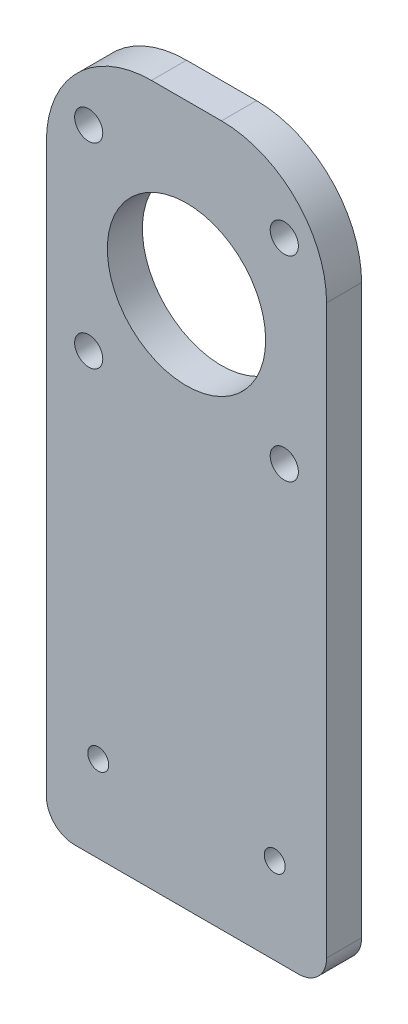
SolidWorks part; units mm, degrees
ref_plane "Front Plane" through (0, 0, 0) normal (0, 0, 1) x (1, 0, 0)
ref_plane "Top Plane" through (0, 0, 0) normal (0, 1, 0) x (1, 0, 0)
ref_plane "Right Plane" through (0, 0, 0) normal (1, 0, 0) x (0, 0, -1)
sketch "Sketch2" plane through (0, 0, 0) normal (0, 0, 1) x (1, 0, 0)
  line L0 (41.4, 15.6363) -> (9.4, 15.6363) construction
  line L1 (0, 0) -> (50.8, 0)
  line L2 (0, 0) -> (0, 127)
  line L3 (0, 127) -> (50.8, 127)
  line L4 (50.8, 0) -> (50.8, 127)
  circle A0 centre (25.4, 96.5708) radius 14.351
  circle A1 centre (43.1292, 114.3) radius 2.5527
  circle A2 centre (7.6708, 114.3) radius 2.5527
  circle A3 centre (7.6708, 78.8416) radius 2.5527
  circle A4 centre (43.1292, 78.8416) radius 2.5527
  circle A5 centre (41.4, 15.6363) radius 1.905
  circle A6 centre (9.4, 15.6363) radius 1.905
  point P19 (25.4, 15.6363)
  point P20 (25.4, 0)
  dimension "D4" = 28.702
  dimension "D5" = 5.1054
  dimension "D7" = 5.1054
  dimension "D8" = 5.1054
  dimension "D9" = 5.1054
  dimension "D3" = 35.4584
  dimension "D6" = 35.4584
  dimension "D12" = 12.7
  dimension "D16" = 3.81
  dimension "D17" = 3.81
  dimension "D18" = 32
  dimension "D1" = 127
  dimension "D2" = 50.8
  dimension "D10" = 35.4584
  dimension "D11" = 35.4584
  dimension "D13" = 17.7292
  dimension "D14" = 17.7292
  dimension "D15" = 17.7292
extrude "Boss-Extrude3" add sketch "Sketch2" along normal blind 6.35
fillet "Fillet1" radius 19.05 1 edges at (50.8, 127, 3.175)
fillet "Fillet4" radius 19.05 1 edges at (0, 127, 3.175)
fillet "Fillet5" radius 5.08 2 edges at (0, 0, 3.175) (50.8, 0, 3.175)
